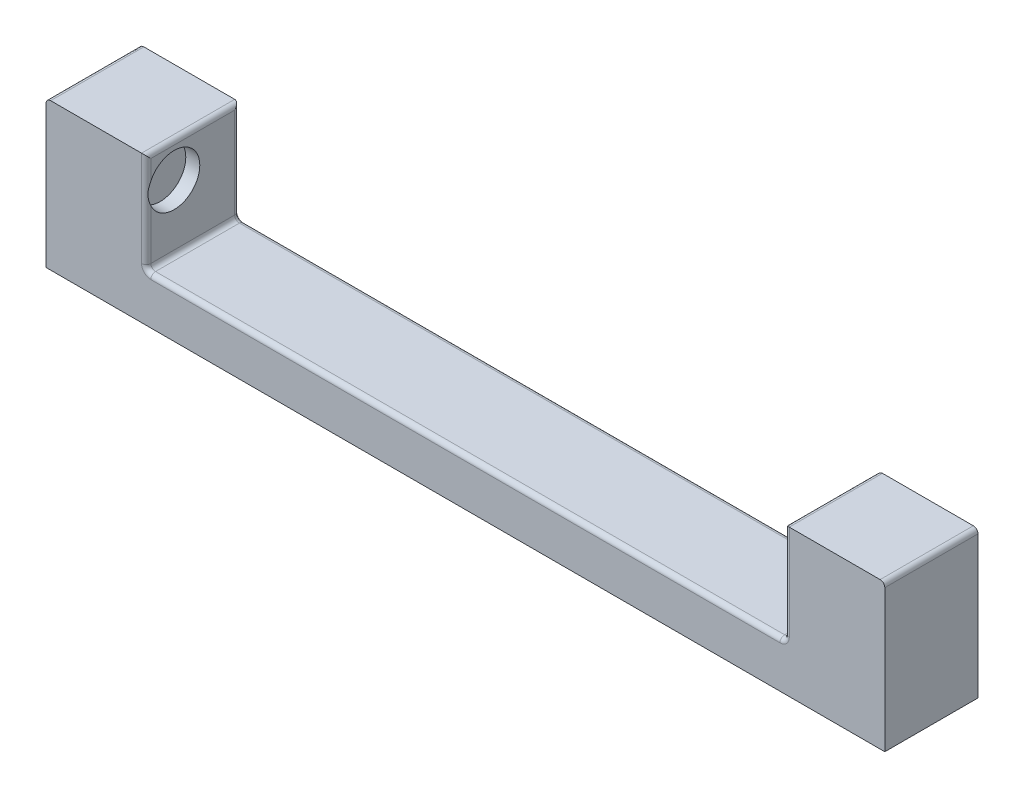
SolidWorks part; units mm, degrees
ref_plane "Plan de face" through (0, 0, 0) normal (0, 0, 1) x (1, 0, 0)
ref_plane "Plan de dessus" through (0, 0, 0) normal (0, 1, 0) x (1, 0, 0)
ref_plane "Plan de droite" through (0, 0, 0) normal (1, 0, 0) x (0, 0, -1)
sketch "Esquisse1" plane through (0, 0, 0) normal (0, 0, 1) x (1, 0, 0)
  line L0 (0, -55) -> (0, 55) construction
  line L1 (-34.25, 10.75) -> (-45, 10.75)
  line L2 (-34.25, 10.75) -> (-34.25, 0)
  line L3 (-34.25, 0) -> (-45, 0)
  line L4 (-45, 10.75) -> (-45, 0)
  line L5 (34.25, 0) -> (45, 0)
  line L6 (45, 10.75) -> (45, 0)
  line L7 (34.25, 10.75) -> (45, 10.75)
  line L8 (34.25, 10.75) -> (34.25, 0)
  dimension "D1" = 10.75
  dimension "D2" = 34.25
extrude "Boss.-Extru.1" add sketch "Esquisse1" along normal blind 10
sketch "Esquisse3" plane through (0, 0, 0) normal (0, -1, 0) x (1, 0, 0)
  line L1 (-45, 10) -> (45, 10)
  line L2 (-45, 10) -> (-45, 0)
  line L3 (-45, 0) -> (45, 0)
  line L4 (45, 10) -> (45, 0)
extrude "Boss.-Extru.2" add sketch "Esquisse3" along normal blind 5
sketch "Esquisse4" plane through (-34.25, 0, 0) normal (1, 0, 0) x (0, 0, -1)
  line L3 (-10, 0) -> (0, 0) construction
  line L4 (0, 0) -> (0, 10.75) construction
  circle A0 centre (-7, 7) radius 2.75
  dimension "D1" = 5.5
  dimension "D2" = 7
  dimension "D3" = 7
extrude "Enlèv. mat.-Extru.1" cut sketch "Esquisse4" against normal blind 1.5
mirror "Symétrie1" about plane through (0, 0, 0) normal (1, 0, 0) of "Enlèv. mat.-Extru.1"
fillet "Congé1" radius 0.5 12 edges at (-34.25, 5.375, 0) (34.25, 5.375, 0) (34.25, 5.375, 10) (-34.25, 5.375, 10) (0, 0, 0) (0, 0, 10) (45, 10.75, 5) (34.25, 10.75, 5) (34.25, 0, 5) (-45, 10.75, 5) (-34.25, 10.75, 5) (-34.25, 0, 5)
